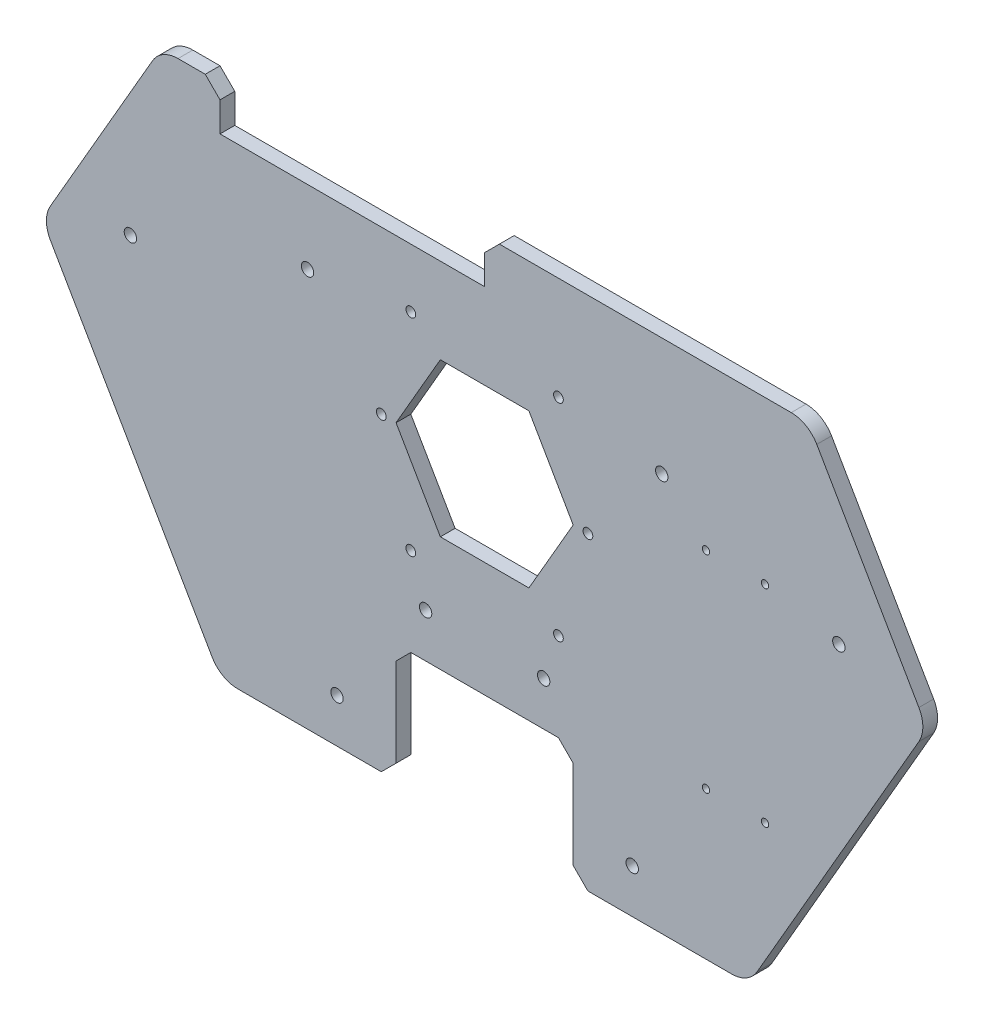
SolidWorks part; units mm, degrees
material "5052-O"
ref_plane "前基準面" through (0, 0, 0) normal (0, 0, 1) x (1, 0, 0)
ref_plane "上基準面" through (0, 0, 0) normal (0, 1, 0) x (1, 0, 0)
ref_plane "右基準面" through (0, 0, 0) normal (1, 0, 0) x (0, 0, -1)
sketch "草圖1" plane through (0, 0, 0) normal (0, 0, 1) x (1, 0, 0)
  line L1 (150, 0) -> (75, 129.9038)
  line L2 (75, 129.9038) -> (-75, 129.9038)
  line L3 (-75, 129.9038) -> (-150, 0)
  line L4 (-150, 0) -> (-75, -129.9038)
  line L5 (-75, -129.9038) -> (75, -129.9038)
  line L6 (75, -129.9038) -> (150, 0)
  circle A0 centre (0, 0) radius 129.9038 construction
  dimension "D1" = 150
extrude "填料-伸長1" add sketch "草圖1" along normal blind 5
ref_axis "基準軸1" through (0, 0, 0) along (0, 0, 1)
sketch "草圖3" plane through (0, 0, 5) normal (0, 0, 1) x (1, 0, 0)
  line L0 (-109.641, 69.9038) -> (-89.641, 69.9038)
  line L1 (-75, 129.9038) -> (-150, 0) construction
  line L2 (-89.641, 69.9038) -> (-89.641, 54.9038)
  line L3 (-89.641, 54.9038) -> (0, 54.9038)
  line L4 (0, 54.9038) -> (0, 69.9038)
  line L5 (0, 69.9038) -> (109.641, 69.9038)
  line L6 (150, 0) -> (75, 129.9038) construction
  line L7 (75, 129.9038) -> (-75, 129.9038) construction
  point P16 (0, 129.9038)
  dimension "D1" = 75
  dimension "D2" = 15
  dimension "D4" = 20
extrude "除料-伸長2" cut sketch "草圖3" against normal through all and the other way through all
sketch "草圖4" plane through (0, 0, 5) normal (0, 0, 1) x (1, 0, 0)
  line L1 (30, 0) -> (15, 25.9808)
  line L2 (15, 25.9808) -> (-15, 25.9808)
  line L3 (-15, 25.9808) -> (-30, 0)
  line L4 (-30, 0) -> (-15, -25.9808)
  line L5 (-15, -25.9808) -> (15, -25.9808)
  line L6 (15, -25.9808) -> (30, 0)
  circle A0 centre (0, 0) radius 25.9808 construction
  dimension "D1" = 30
extrude "除料-伸長3" cut sketch "草圖4" against normal up to next
chamfer "導角1" distance 5 angle 45 2 edges at (0, 69.9038, 2.5) (-89.641, 69.9038, 2.5)
sketch "草圖5" plane through (0, 0, 5) normal (0, 0, 1) x (1, 0, 0)
  line L0 (-89.4338, -104.9038) -> (-30, -104.9038)
  line L1 (-150, 0) -> (-75, -129.9038) construction
  line L2 (-30, -104.9038) -> (-30, -64.9038)
  line L3 (-30, -64.9038) -> (30, -64.9038)
  line L4 (30, -64.9038) -> (30, -104.9038)
  line L5 (30, -104.9038) -> (89.4338, -104.9038)
  line L6 (75, -129.9038) -> (150, 0) construction
  line L7 (-75, -129.9038) -> (75, -129.9038) construction
  dimension "D1" = 25
  dimension "D2" = 40
  dimension "D3" = 60
extrude "除料-伸長6" cut sketch "草圖5" against normal through all and the other way through all flip side to cut
chamfer "導角2" distance 5 angle 45 4 edges at (30, -104.9038, 2.5) (30, -64.9038, 2.5) (-30, -64.9038, 2.5) (-30, -104.9038, 2.5)
sketch "草圖6" plane through (0, 0, 5) normal (0, 0, 1) x (1, 0, 0)
  circle A0 centre (-50, -90) radius 2.1
  circle A1 centre (-120, 10) radius 2.1
  circle A2 centre (-60, 30) radius 2.1
  circle A3 centre (-20, -50) radius 2.1
  dimension "D1" = 4.2
  dimension "D2" = 4.2
  dimension "D7" = 4.2
  dimension "D8" = 4.2
  dimension "D3" = 50
  dimension "D4" = 90
  dimension "D5" = 120
  dimension "D6" = 10
  dimension "D9" = 50
  dimension "D10" = 20
  dimension "D11" = 30
  dimension "D12" = 60
extrude "除料-伸長7" cut sketch "草圖6" against normal up to next
mirror "鏡射1" about plane through (0, 0, 0) normal (1, 0, 0) of "除料-伸長7"
fillet "圓角1" radius 10 6 edges at (109.641, 69.9038, 2.5) (150, 0, 2.5) (89.4338, -104.9038, 2.5) (-89.4338, -104.9038, 2.5) (-150, 0, 2.5) (-109.641, 69.9038, 2.5)
hole_wizard "M3x0.5 螺紋孔1" positions "草圖12" profile "草圖13" tap size "M3x0.5" standard "Ansi Metric"
sketch "草圖12" plane through (0, 0, 5) normal (0, 0, 1) x (1, 0, 0)
  line L1 (75, -54.9038) -> (95, -54.9038) construction
  line L2 (75, -54.9038) -> (75, 15.0962) construction
  line L3 (75, 15.0962) -> (95, 15.0962) construction
  line L4 (95, -54.9038) -> (95, 15.0962) construction
  line L5 (75, -54.9038) -> (95, 15.0962) construction
  line L6 (75, 15.0962) -> (95, -54.9038) construction
  line L7 (83.6603, -104.9038) -> (35, -104.9038) construction
  point P2 (95, 15.0962)
  point P63 (75, -54.9038)
  point P64 (75, 15.0962)
  point P65 (95, -54.9038)
  dimension "D1" = 70
  dimension "D2" = 20
  dimension "D3" = 50
  dimension "D4" = 75
sketch "草圖13" plane through (95, 15.0962, 5) normal (1, 0, 0) x (0, -1, 0)
  line L0 (0, 0) -> (0, 9.2511)
  line L1 (0, 9.2511) -> (1.25, 8.5)
  line L2 (1.25, 8.5) -> (1.25, 0)
  line L5 (1.25, 0) -> (0, 0)
  line L10 (0, 9.2511) -> (-1.25, 8.5) construction
  line L11 (0, -6.35) -> (0, 107.95) construction
  dimension "螺孔鑽直徑" = 2.5
  dimension "螺孔鑽深度" = 8.5
  dimension "導頭角度" = 118
cosmetic thread "鑽孔螺紋5" parameters "D1"=6, "D2"=3
cosmetic thread "鑽孔螺紋6" parameters "D1"=6, "D2"=3
cosmetic thread "鑽孔螺紋7" parameters "D1"=6, "D2"=3
cosmetic thread "鑽孔螺紋8" parameters "D1"=6, "D2"=3
hole_wizard "M4x0.7 螺紋孔2" positions "草圖17" profile "草圖18" tap size "M4x0.7" standard "Ansi Metric"
sketch "草圖17" plane through (0, 0, 5) normal (0, 0, 1) x (1, 0, 0)
  line L1 (-25, -35) -> (25, -35) construction
  line L2 (-25, -35) -> (-25, 35) construction
  line L3 (-25, 35) -> (25, 35) construction
  line L4 (25, -35) -> (25, 35) construction
  line L5 (-25, -35) -> (25, 35) construction
  line L6 (-25, 35) -> (25, -35) construction
  point P2 (25, 35)
  point P61 (-25, -35)
  point P62 (-25, 35)
  point P63 (25, -35)
  point P74 (-35, 0)
  point P76 (35, 0)
  point P83 (0, 0)
  dimension "D1" = 50
  dimension "D2" = 70
  dimension "D3" = 35
  dimension "D4" = 35
sketch "草圖18" plane through (25, 35, 5) normal (1, 0, 0) x (0, -1, 0)
  line L0 (0, 0) -> (0, 12.4914)
  line L1 (0, 12.4914) -> (1.65, 11.5)
  line L2 (1.65, 11.5) -> (1.65, 0)
  line L5 (1.65, 0) -> (0, 0)
  line L10 (0, 12.4914) -> (-1.65, 11.5) construction
  line L11 (0, -6.35) -> (0, 107.95) construction
  dimension "螺孔鑽直徑" = 3.3
  dimension "螺孔鑽深度" = 11.5
  dimension "導頭角度" = 118
cosmetic thread "鑽孔螺紋9" parameters "D1"=8, "D2"=4
cosmetic thread "鑽孔螺紋10" parameters "D1"=8, "D2"=4
cosmetic thread "鑽孔螺紋11" parameters "D1"=8, "D2"=4
cosmetic thread "鑽孔螺紋12" parameters "D1"=8, "D2"=4
cosmetic thread "鑽孔螺紋13" parameters "D1"=8, "D2"=4
cosmetic thread "鑽孔螺紋14" parameters "D1"=8, "D2"=4
